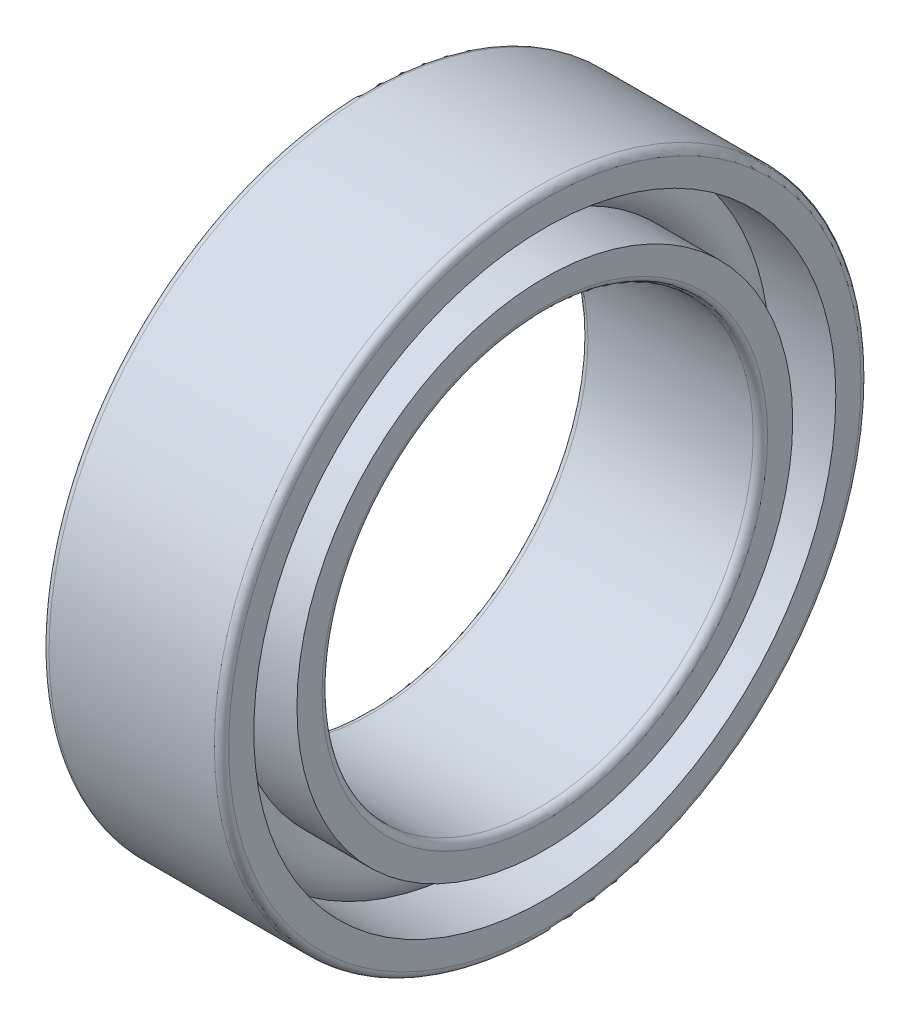
SolidWorks part; units mm, degrees
ref_plane "Plane1" through (0, 0, 0) normal (0, 0, 1) x (1, 0, 0)
ref_plane "Plane2" through (0, 0, 0) normal (0, 1, 0) x (1, 0, 0)
ref_plane "Plane3" through (0, 0, 0) normal (1, 0, 0) x (0, 0, -1)
sketch "Clipboard" plane through (0, 0, 0) normal (0, 0, 1) x (1, 0, 0)
  line L0 (-10, 0) -> (10, 0) construction
  line L1 (0, 0) -> (22.3471, -0.7804)
  line L2 (0, 0) -> (7.4954, 0.2617)
  line L3 (0, 0) -> (22.3471, -0.7804)
  line L4 (0, 0) -> (-22.3573, -0.3902)
sketch "CagSpiSke" plane through (0, 0, 0) normal (0, 0, 1) x (1, 0, 0)
  line L0 (0.09, 7.35) -> (0.09, 7.65)
  line L1 (0.09, 7.65) -> (-0.09, 7.65)
  line L2 (-0.09, 7.65) -> (-0.09, 7.35)
  line L3 (-0.09, 7.35) -> (0.09, 7.35)
  line L4 (-20.6375, 0) -> (20.6375, 0) construction
  line L5 (0, 0) -> (0, 23.7692) construction
revolve "CageSpine" add sketch "CagSpiSke" angle 0.001 about L4 reverse direction yes
ref_axis "Axis1" through (-50, 0, 0) along (1, 0, 0)
sketch "CagBalSke" plane through (0, 0, 0) normal (0, 0, 1) x (1, 0, 0)
  line L0 (-0.99, 7.5) -> (0.99, 7.5)
  line L1 (-1.905, 7.5) -> (1.905, 7.5) construction
  line L2 (-10, 0) -> (10, 0) construction
  line L3 (0, 0) -> (0, 24) construction
  arc A0 (0.99, 7.5) -> (-0.99, 7.5) centre (0, 7.5) cw
revolve "CageBall" [suppressed] add sketch "CagBalSke" angle 360 about L1 reverse direction yes
pattern_circular "CageBalls" [suppressed] count 2 every 180 about axis through (-50, 0, 0) along (1, 0, 0)
sketch "CagTrmODSke" plane through (0, 0, 0) normal (0, 0, 1) x (1, 0, 0)
  line L0 (0.991, 7.65) -> (0.991, 8.491)
  line L1 (0.991, 8.491) -> (-0.991, 8.491)
  line L2 (-0.991, 8.491) -> (-0.991, 7.65)
  line L3 (-0.991, 7.65) -> (0.991, 7.65)
  line L4 (-20.6375, 0) -> (20.6375, 0) construction
  line L5 (0, 0) -> (0, 25) construction
revolve "CageTrimOD" [suppressed] cut sketch "CagTrmODSke" angle 360 about L4 reverse direction yes
sketch "CagTrmIDSke" plane through (0, 0, 0) normal (0, 0, 1) x (1, 0, 0)
  line L0 (0.991, 6.511) -> (0.991, 7.35)
  line L1 (0.991, 7.35) -> (-0.991, 7.35)
  line L2 (-0.991, 7.35) -> (-0.991, 6.511)
  line L3 (-0.991, 6.511) -> (0.991, 6.511)
  line L4 (-20.6375, 0) -> (20.6375, 0) construction
  line L5 (0, 0) -> (0, 25) construction
revolve "CageTrimID" [suppressed] cut sketch "CagTrmIDSke" angle 360 about L4 reverse direction yes
sketch "BalSimSke" plane through (0, 0, 0) normal (0, 0, 1) x (1, 0, 0)
  line L0 (-10, 0) -> (10, 0) construction
  line L1 (-10, 7.5) -> (10, 7.5) construction
  line L2 (0, 0) -> (0, 23) construction
  circle A0 centre (0, 7.5) radius 0.9
revolve "BallsSimplified" add sketch "BalSimSke" angle 360 about L0
sketch "BalDetSke" plane through (0, 0, 0) normal (0, 0, 1) x (1, 0, 0)
  line L0 (-0.9, 7.5) -> (0.9, 7.5)
  line L1 (-1.905, 7.5) -> (1.905, 7.5) construction
  line L2 (0, 0) -> (0, 25) construction
  arc A0 (0.9, 7.5) -> (-0.9, 7.5) centre (0, 7.5) cw
revolve "BallDetailed" [suppressed] add sketch "BalDetSke" angle 360 about L1 reverse direction yes
sketch "InnRacSke" plane through (0, 0, 0) normal (0, 0, 1) x (1, 0, 0)
  line L0 (-0.6369, 6.9) -> (-2.5, 6.9)
  line L1 (-2.5, 6.9) -> (-2.5, 6.2)
  line L2 (-2.3, 6) -> (2.3, 6)
  line L3 (2.5, 6.2) -> (2.5, 6.9)
  line L4 (2.5, 6.9) -> (0.6369, 6.9)
  line L5 (-20.6375, 0) -> (20.6375, 0) construction
  line L6 (0, 0) -> (0, 30) construction
  arc A0 (-2.5, 6.2) -> (-2.3, 6) centre (-2.3, 6.2) ccw
  arc A1 (2.3, 6) -> (2.5, 6.2) centre (2.3, 6.2) ccw
  arc A2 (0.6369, 6.9) -> (-0.6369, 6.9) centre (0, 7.5) cw
revolve "InnerRace" add sketch "InnRacSke" angle 360 about L5 reverse direction yes
sketch "OutRacSke" plane through (0, 0, 0) normal (0, 0, 1) x (1, 0, 0)
  line L0 (-0.6369, 8.1) -> (-2.5, 8.1)
  line L1 (-2.5, 8.1) -> (-2.5, 8.8)
  line L2 (-2.3, 9) -> (2.3, 9)
  line L3 (2.5, 8.8) -> (2.5, 8.1)
  line L4 (2.5, 8.1) -> (0.6369, 8.1)
  line L5 (-20.6375, 0) -> (20.6375, 0) construction
  line L6 (0, 0) -> (0, 30) construction
  arc A0 (-2.5, 8.8) -> (-2.3, 9) centre (-2.3, 8.8) cw
  arc A1 (2.3, 9) -> (2.5, 8.8) centre (2.3, 8.8) cw
  arc A2 (0.6369, 8.1) -> (-0.6369, 8.1) centre (0, 7.5) ccw
revolve "OuterRace" add sketch "OutRacSke" angle 360 about L5 reverse direction yes
pattern_circular "BallsDetailed" [suppressed] count 2 every 180 about axis through (-50, 0, 0) along (1, 0, 0)
equation "\"BallCLRad@Clipboard\" = ( \"OD@OutRacSke\" + \"ID@InnRacSke\" ) / 4"
equation "\"BallCLRad@BalSimSke\" = \"BallCLRad@Clipboard\""
equation "\"BallCLRad@BalDetSke\" = \"BallCLRad@Clipboard\""
equation "\"BallCLRad@InnRacSke\" = \"BallCLRad@Clipboard\""
equation "\"BallCLRad@OutRacSke\" = \"BallCLRad@Clipboard\""
equation "\"Ball_diameter@InnRacSke\" = \"Ball_diameter@BalDetSke\" - 0.05"
equation "\"Ball_diameter@OutRacSke\" = \"Ball_diameter@BalDetSke\" - 0.05"
equation "\"Ball_diameter@BalSimSke\" = \"Ball_diameter@BalDetSke\""
equation "\"Width@OutRacSke\" = \"Width@InnRacSke\""
equation "\"Fillet_radius@OutRacSke\" = \"Fillet_radius@InnRacSke\""
equation "\"Max_count@Clipboard\" = int( 3.14159265 / atn(( \"Ball_diameter@BalDetSke\" / 2) / sqr( \"BallCLRad@Clipboard\"  *  \"BallCLRad@Clipboard\" - ( \"Ball_diameter@BalDetSke\" / 2) *  ( \"Ball_diameter@BalDetSke\" / 2))))"
equation "\"Max_count@Clipboard\" = ((sgn( \"Max_count@Clipboard\" - \"Count@Clipboard\" )-1)*( \"Max_count@Clipboard\" - \"Count@Clipboard\" ))/-2+ \"Count@Clipboard\""
equation "\"Count@BallsDetailed\" = int( \"Show_count@Clipboard\" ) "
equation "\"Count@BallsDetailed\" = ((sgn( \"Count@BallsDetailed\" - \"Max_count@Clipboard\" )-1)*( \"Count@BallsDetailed\" - \"Max_count@Clipboard\" ))/-2+ \"Max_count@Clipboard\""
equation "\"Count@BallsDetailed\" = ((sgn( \"Count@BallsDetailed\" - \"Min_count@Clipboard\" )+1)*( \"Count@BallsDetailed\" - \"Min_count@Clipboard\"))/2 +\"Min_count@Clipboard\""
equation "\"Angle@BallsDetailed\" = 360.0 / \"Max_count@Clipboard\""
equation "\"BallCLRad@CagBalSke\" = \"BallCLRad@Clipboard\""
equation "\"Count@CageBalls\" = \"Count@BallsDetailed\""
equation "\"Angle@CageBalls\" = \"Angle@BallsDetailed\""
equation "\"Angle@CageSpine\" =  \"Angle@CageBalls\" * ( \"Count@CageBalls\" -1 + int( \"Count@CageBalls\" / \"Max_count@Clipboard\" ) )  + 0.001 -  int( \"Count@CageBalls\" / \"Max_count@Clipboard\" ) * 0.001"
equation "\"Angle@CageSpine\" =  \"Angle@CageSpine\" * int( \"Min_count@Clipboard\" / 2) + int(1 / \"Min_count@Clipboard\")  * 0.001"
equation "\"CageWallOD@CagBalSke\" =  \"Ball_diameter@BalDetSke\" * 1.1"
equation "\"Thickness@CagSpiSke\" =  \"Ball_diameter@BalDetSke\" * 0.1"
equation "\"OD@CagTrmODSke\" = \"BallCLRad@Clipboard\" * 2 + \"CageWallOD@CagBalSke\" + 0.002"
equation "\"ID@CagTrmODSke\" = \"BallCLRad@Clipboard\" * 2 + \"Ball_diameter@BalDetSke\" / 6"
equation "\"OD@CagTrmIDSke\" = \"BallCLRad@Clipboard\" * 2 - \"Ball_diameter@BalDetSke\" / 6"
equation "\"ID@CagTrmIDSke\" = \"BallCLRad@Clipboard\" * 2 - \"CageWallOD@CagBalSke\" + 0.002"
equation "\"OD@CagSpiSke\" = \"ID@CagTrmODSke\""
equation "\"ID@CagSpiSke\" = \"OD@CagTrmIDSke\""
equation "\"Width@CagTrmODSke\" = \"CageWallOD@CagBalSke\" + 0.002"
equation "\"Width@CagTrmIDSke\" = \"CageWallOD@CagBalSke\" + 0.002"
